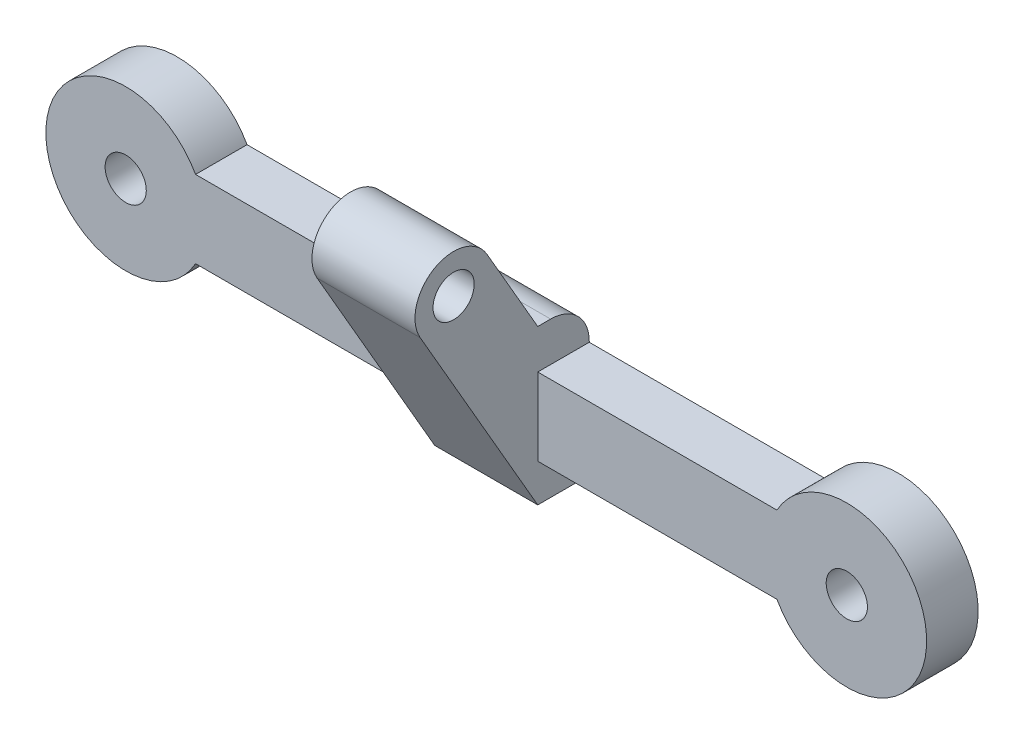
SolidWorks part; units mm, degrees
ref_plane "Alzado" through (0, 0, 0) normal (0, 0, 1) x (1, 0, 0)
ref_plane "Planta" through (0, 0, 0) normal (0, 1, 0) x (1, 0, 0)
ref_plane "Vista lateral" through (0, 0, 0) normal (1, 0, 0) x (0, 0, -1)
sketch "Croquis1" plane through (0, 0, 0) normal (0, 0, 1) x (1, 0, 0)
  line L0 (5.4259, -3) -> (50.5741, -3)
  line L1 (5.4259, 3) -> (50.5741, 3)
  circle A0 centre (0, 0) radius 1.6
  arc A1 (50.5741, -3) -> (50.5741, 3) centre (56, 0) ccw
  arc A2 (5.4259, 3) -> (5.4259, -3) centre (0, 0) ccw
  circle A3 centre (56, 0) radius 1.6
  dimension "D1" = 3.2
  dimension "D3" = 12.4
  dimension "D4" = 2
  dimension "D2" = 2
extrude "Saliente-Extruir1" add sketch "Croquis1" along normal blind 4
ref_plane "Plano1" through (28, 0, 0) normal (1, 0, 0) x (0, 0, -1)
sketch "Croquis2" plane through (28, 0, 0) normal (1, 0, 0) x (0, 0, -1)
  line L0 (-4, -5.9398) -> (-13.1332, 9.8794)
  line L2 (-7.5352, 11.3794) -> (-13.5352, 11.3794) construction
  line L3 (-4, 6.0602) -> (0, 6.0602)
  line L4 (-4, -5.9398) -> (0, -5.9398)
  line L5 (0, 6.0602) -> (0, -5.9398)
  line L7 (-4, 6.0602) -> (-7.9371, 12.8794)
  circle A0 centre (-10.5352, 11.3794) radius 1.6
  arc A1 (-7.9371, 12.8794) -> (-13.1332, 9.8794) centre (-10.5352, 11.3794) ccw
  dimension "D4" = 3.2
  dimension "D5" = 6
  dimension "D1" = 4
extrude "Saliente-Extruir2" add sketch "Croquis2" along normal blind 4 and the other way blind 4
fillet "Redondeo1" radius 3 1 edges at (28, 6.0602, 0)
